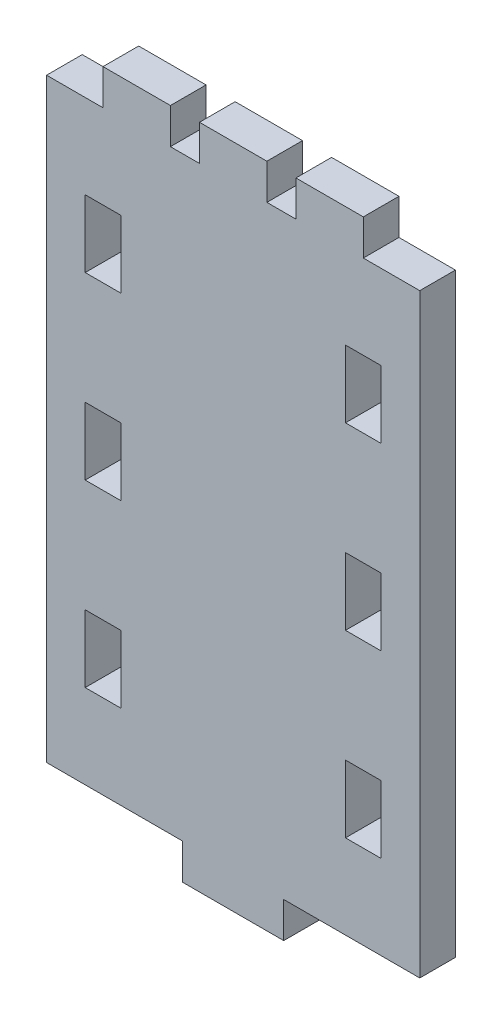
SolidWorks part; units mm, degrees
ref_plane "Front Plane" through (0, 0, 0) normal (0, 0, 1) x (1, 0, 0)
ref_plane "Top Plane" through (0, 0, 0) normal (0, 1, 0) x (1, 0, 0)
ref_plane "Right Plane" through (0, 0, 0) normal (1, 0, 0) x (0, 0, -1)
sketch "Sketch1" plane through (0, 0, 0) normal (0, 0, 1) x (1, 0, 0)
  line L0 (0, 0) -> (-12.1125, 0)
  line L1 (-12.1125, 0) -> (-12.1125, -3.175)
  line L2 (-12.1125, -3.175) -> (-21.1125, -3.175)
  line L3 (-21.1125, -3.175) -> (-21.1125, 0)
  line L4 (-21.1125, 0) -> (-33.225, 0)
  line L5 (-33.225, 0) -> (-33.225, 53)
  line L6 (-33.225, 53) -> (-28.2, 53)
  line L7 (-28.2, 53) -> (-28.2, 56.175)
  line L8 (-28.2, 56.175) -> (-22.2, 56.175)
  line L9 (-22.2, 56.175) -> (-22.2, 53)
  line L10 (-22.2, 53) -> (-19.6125, 53)
  line L11 (-19.6125, 53) -> (-19.6125, 56.175)
  line L12 (-19.6125, 56.175) -> (-13.6125, 56.175)
  line L13 (-13.6125, 56.175) -> (-13.6125, 53)
  line L14 (-13.6125, 53) -> (-11.025, 53)
  line L15 (-11.025, 53) -> (-11.025, 56.175)
  line L16 (-11.025, 56.175) -> (-5.025, 56.175)
  line L17 (-5.025, 56.175) -> (-5.025, 53)
  line L18 (-5.025, 53) -> (0, 53)
  line L19 (0, 53) -> (0, 0)
  line L20 (-16.6125, 57.9063) -> (-16.6125, -10.4437) construction
  line L21 (-16.6125, 56.175) -> (-16.6125, 48.5189) construction
  line L22 (-3.4375, 13.5) -> (-3.4375, 7.5)
  line L23 (-3.4375, 13.5) -> (-6.6125, 13.5)
  line L24 (-6.6125, 13.5) -> (-6.6125, 7.5)
  line L25 (-6.6125, 7.5) -> (-3.4375, 7.5)
  line L26 (0, 26.5) -> (-5.025, 26.5) construction
  line L27 (-5.025, 13.5) -> (-5.025, 23.5) construction
  line L28 (-5.025, 23.5) -> (-3.4375, 23.5)
  line L29 (-3.4375, 23.5) -> (-3.4375, 29.5)
  line L30 (-3.4375, 29.5) -> (-6.6125, 29.5)
  line L31 (-6.6125, 29.5) -> (-6.6125, 23.5)
  line L32 (-6.6125, 23.5) -> (-5.025, 23.5)
  line L33 (-5.025, 29.5) -> (-5.025, 39.5) construction
  line L34 (-5.025, 39.5) -> (-3.4375, 39.5)
  line L35 (-3.4375, 39.5) -> (-3.4375, 45.5)
  line L36 (-3.4375, 45.5) -> (-6.6125, 45.5)
  line L37 (-6.6125, 45.5) -> (-6.6125, 39.5)
  line L38 (-6.6125, 39.5) -> (-5.025, 39.5)
  line L39 (-28.2, 29.5) -> (-28.2, 39.5) construction
  line L40 (-28.2, 13.5) -> (-28.2, 23.5) construction
  line L41 (-26.6125, 39.5) -> (-28.2, 39.5)
  line L42 (-26.6125, 45.5) -> (-26.6125, 39.5)
  line L43 (-29.7875, 45.5) -> (-26.6125, 45.5)
  line L44 (-5.025, 45.5) -> (-5.025, 53) construction
  line L45 (-29.7875, 39.5) -> (-29.7875, 45.5)
  line L46 (-28.2, 39.5) -> (-29.7875, 39.5)
  line L47 (-26.6125, 23.5) -> (-28.2, 23.5)
  line L48 (-26.6125, 29.5) -> (-26.6125, 23.5)
  line L49 (-29.7875, 29.5) -> (-26.6125, 29.5)
  line L50 (-29.7875, 23.5) -> (-29.7875, 29.5)
  line L51 (-28.2, 23.5) -> (-29.7875, 23.5)
  line L52 (-26.6125, 7.5) -> (-29.7875, 7.5)
  line L53 (-26.6125, 13.5) -> (-26.6125, 7.5)
  line L54 (-29.7875, 13.5) -> (-26.6125, 13.5)
  line L55 (-5.025, 7.5) -> (-5.025, 0) construction
  line L56 (-29.7875, 13.5) -> (-29.7875, 7.5)
  line L61 (-5, 26.5) -> (-25.6701, 26.5) construction
  dimension "D1" = 3.175
  dimension "D2" = 3.4375
  dimension "D3" = 9
  dimension "D4" = 20
  dimension "D5" = 6
  dimension "D8" = 3.175
  dimension "D9" = 6
  dimension "D10" = 10
  dimension "D13" = 53
extrude "Boss-Extrude1" add sketch "Sketch1" along normal mid plane 3.175
